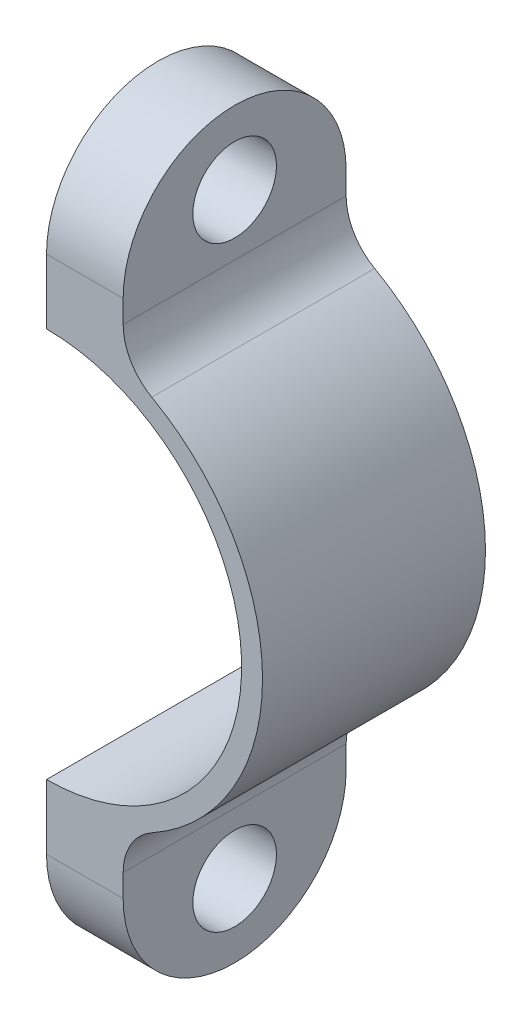
SolidWorks part; units mm, degrees
note: '?' marks a value the reader was unsure of.
material "7075-T6 (SN)"
ref_plane "Płaszczyzna przednia" through (0, 0, 0) normal (0, 0, 1) x (1, 0, 0)
ref_plane "Płaszczyzna górna" through (0, 0, 0) normal (0, 1, 0) x (1, 0, 0)
ref_plane "Płaszczyzna prawa" through (0, 0, 0) normal (1, 0, 0) x (0, 0, -1)
sketch "Szkic1" plane through (0, 0, 0) normal (0, 0, 1) x (1, 0, 0)
  line L0 (0, 15.5) -> (0, 14)
  line L1 (0, -14) -> (0, -15.5)
  arc A0 (0, -14) -> (0, 14) centre (0, 0) ccw
  arc A1 (0, -15.5) -> (0, 15.5) centre (0, 0) ccw
  dimension "D1" = 14
  dimension "D2" = 15.5
extrude "Dodanie-wyciągnięcie1" add sketch "Szkic1" along normal blind 16
sketch "Szkic2" plane through (0, 0, 0) normal (-1, 0, 0) x (0, 0, 1)
  line L0 (0, 18.65) -> (0, 14)
  line L1 (0, 14) -> (16, 14)
  line L2 (16, 14) -> (16, 18.65)
  line L3 (16, 15.5) -> (0, 15.5) construction
  line L4 (16, 0) -> (0, 0)
  line L5 (16, -14) -> (16, 14) construction
  line L6 (16, -14) -> (16, -18.65)
  line L7 (0, -18.65) -> (0, -14)
  line L8 (0, -14) -> (16, -14)
  line L9 (8, 0) -> (8, 21.4) construction
  circle A0 centre (8, 21.4) radius 5.25
  circle A1 centre (8, 21.4) radius 3
  circle A2 centre (8, -21.4) radius 3
  arc A3 (16, -18.65) -> (0, -18.65) centre (8, -18.65) cw
  arc A4 (16, 18.65) -> (0, 18.65) centre (8, 18.65) ccw
  dimension "D1" = 16
  dimension "D2" = 6
  dimension "D4" = 1.5
  dimension "D5" = 10.5
  dimension "D6" = 21.4
  dimension "D7" = 16
  dimension "D3" = 90
extrude "Dodanie-wyciągnięcie2" add sketch "Szkic2" against normal blind 5.5
fillet "Zaokrąglenie1" radius 1.5 1 edges at (14, 0, 0)
chamfer "Sfazowanie1" [suppressed] distance 0.5 angle 45
fillet "Zaokrąglenie2" radius 4 2 edges at (5.5, -14.4914, 8) (5.5, 14.4914, 8)
ref_axis "Oś1" through (5.5, -21.4, 8) along (-1, 0, 0)?
ref_axis "Oś2" through (-0.5384, 21.4, 8) along (-1, 0, 0)?
